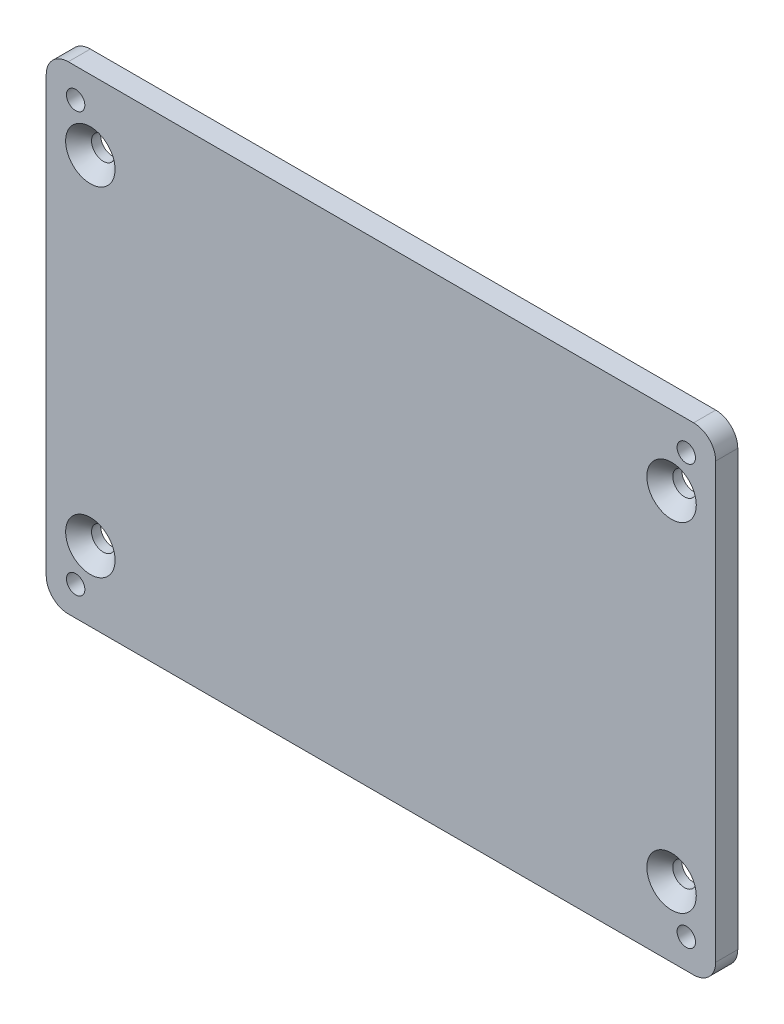
SolidWorks part; units mm, degrees
material "6061-T6 (SS)"
ref_plane "Front Plane" through (0, 0, 0) normal (0, 0, 1) x (1, 0, 0)
ref_plane "Top Plane" through (0, 0, 0) normal (0, 1, 0) x (1, 0, 0)
ref_plane "Right Plane" through (0, 0, 0) normal (1, 0, 0) x (0, 0, -1)
sketch "Sketch1" plane through (0, 0, 0) normal (0, 0, 1) x (1, 0, 0)
  line L1 (45.5, -32.5) -> (-45.5, -32.5)
  line L2 (45.5, -32.5) -> (45.5, 32.5)
  line L3 (45.5, 32.5) -> (-45.5, 32.5)
  line L4 (-45.5, -32.5) -> (-45.5, 32.5)
  line L5 (45.5, -32.5) -> (-45.5, 32.5) construction
  line L6 (45.5, 32.5) -> (-45.5, -32.5) construction
  point P0 (0, 0)
  dimension "D1" = 91
  dimension "D2" = 65
extrude "Boss-Extrude1" add sketch "Sketch1" along normal blind 3
sketch "Sketch2" plane through (0, 0, 3) normal (0, 0, 1) x (1, 0, 0)
  line L1 (41.5, -28.5) -> (-41.5, -28.5)
  line L2 (41.5, -28.5) -> (41.5, 28.5)
  line L3 (41.5, 28.5) -> (-41.5, 28.5)
  line L4 (-41.5, -28.5) -> (-41.5, 28.5)
  line L5 (41.5, -28.5) -> (-41.5, 28.5) construction
  line L6 (41.5, 28.5) -> (-41.5, -28.5) construction
  point P0 (0, 0)
  dimension "D1" = 57
  dimension "D2" = 83
hole_wizard "Tap Drill for M3x0.5 Tap1" positions "Sketch3" profile "Sketch4" hole size "M3x0.5" standard "ANSI Metric" end condition through all
sketch "Sketch3" plane through (0, 0, 3) normal (0, 0, 1) x (1, 0, 0)
  point P0 (-41.5, 28.5)
  point P3 (41.5, 28.5)
  point P6 (41.5, -28.5)
  point P9 (-41.5, -28.5)
sketch "Sketch4" plane through (-41.5, 28.5, 3) normal (1, 0, 0) x (0, -1, 0)
  line L0 (0, 0) -> (0, 3)
  line L1 (0, 3) -> (1.25, 3)
  line L2 (1.25, 3) -> (1.25, 0)
  line L5 (1.25, 0) -> (0, 0)
  line L11 (0, -6.35) -> (0, 107.95) construction
  dimension "Thru Hole Dia." = 2.5
  dimension "Thru Hole Depth" = 3
fillet "Fillet1" radius 3 4 edges at (45.5, 32.5, 1.5) (45.5, -32.5, 1.5) (-45.5, -32.5, 1.5) (-45.5, 32.5, 1.5)
sketch "Sketch5" plane through (0, 0, 3) normal (0, 0, 1) x (1, 0, 0)
  line L0 (-45.5, 29.5) -> (-45.5, -29.5) construction
  line L1 (39.5, -23) -> (-39.5, -23)
  line L2 (39.5, -23) -> (39.5, 23)
  line L3 (39.5, 23) -> (-39.5, 23)
  line L4 (-39.5, -23) -> (-39.5, 23)
  line L5 (39.5, -23) -> (-39.5, 23) construction
  line L6 (39.5, 23) -> (-39.5, -23) construction
  point P0 (0, 0)
  dimension "D1" = 6
  dimension "D2" = 46
hole_wizard "CSK for M3 SFHCS1" positions "Sketch6" profile "Sketch7" countersink size "M3" standard "ANSI Metric" end condition through all
sketch "Sketch6" plane through (0, 0, 3) normal (0, 0, 1) x (1, 0, 0)
  point P0 (-39.5, 23)
  point P3 (-39.5, -23)
  point P6 (39.5, -23)
  point P9 (39.5, 23)
sketch "Sketch7" plane through (-39.5, 23, 3) normal (1, 0, 0) x (0, -1, 0)
  line L0 (0, 0) -> (0, 3)
  line L1 (0, 3) -> (1.6, 3)
  line L2 (1.6, 3) -> (1.6, 1.76)
  line L3 (1.6, 1.76) -> (3.36, 0)
  line L5 (3.36, 0) -> (0, 0)
  line L6 (-1.6, 1.76) -> (-3.36, 0) construction
  line L11 (0, -6.35) -> (0, 107.95) construction
  dimension "Thru Hole Dia." = 3.2
  dimension "Thru Hole Depth" = 3
  dimension "Near C'Sink Dia." = 6.72
  dimension "Near C'Sink Angle" = 90
